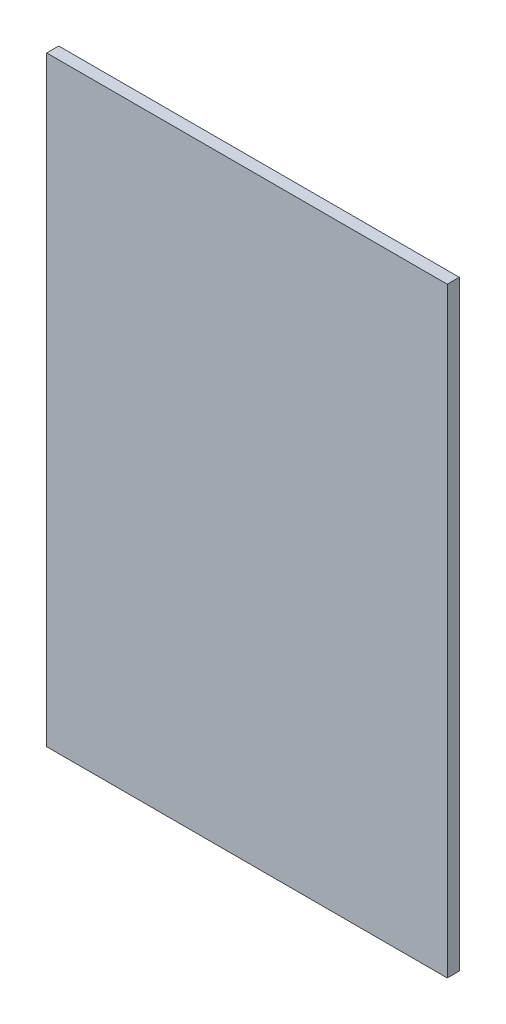
SolidWorks part; units mm, degrees
material "PET"
ref_plane "Front Plane" through (0, 0, 0) normal (0, 0, 1) x (1, 0, 0)
ref_plane "Top Plane" through (0, 0, 0) normal (0, 1, 0) x (1, 0, 0)
ref_plane "Right Plane" through (0, 0, 0) normal (1, 0, 0) x (0, 0, -1)
sketch "Sketch1" plane through (0, 0, 0) normal (0, 0, 1) x (1, 0, 0)
  line L1 (-28.5714, 277.1048) -> (171.4286, 277.1048)
  line L2 (-28.5714, 277.1048) -> (-28.5714, -22.8952)
  line L3 (-28.5714, -22.8952) -> (171.4286, -22.8952)
  line L4 (171.4286, 277.1048) -> (171.4286, -22.8952)
  dimension "D1" = 300
  dimension "D2" = 200
extrude "Boss-Extrude1" add sketch "Sketch1" along normal blind 6
